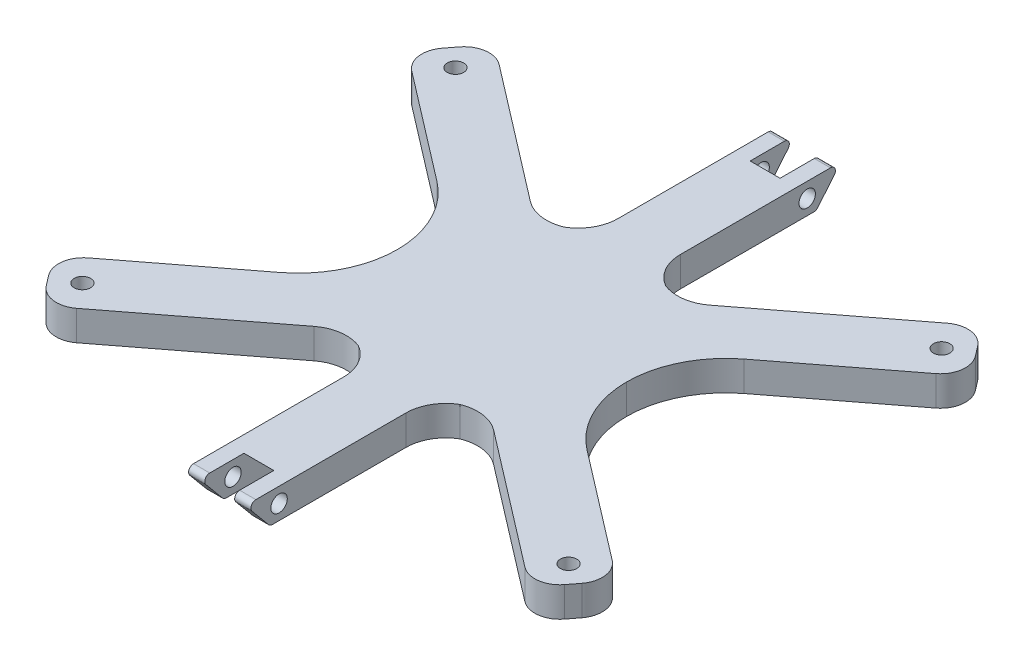
SolidWorks part; units mm, degrees
ref_plane "Front Plane" through (0, 0, 0) normal (0, 0, 1) x (1, 0, 0)
ref_plane "Top Plane" through (0, 0, 0) normal (0, 1, 0) x (1, 0, 0)
ref_plane "Right Plane" through (0, 0, 0) normal (1, 0, 0) x (0, 0, -1)
sketch "Sketch1" plane through (0, 0, 0) normal (0, 1, 0) x (1, 0, 0)
  circle A0 centre (0, 0) radius 23
  dimension "D1" = 46
extrude "Boss-Extrude1" add sketch "Sketch1" along normal mid plane 6
sketch "Sketch2" plane through (0, 0, 0) normal (0, 1, 0) x (1, 0, 0)
  line L0 (-21.3653, 8.5162) -> (-56.5628, 35.5242)
  line L1 (0.2695, -0.2068) -> (-63.7589, 48.924) construction
  line L2 (-48.9532, 45.4411) -> (-13.7557, 18.4331)
  line L3 (0, 37.6664) -> (0, -25.0328) construction
  line L4 (-48.9532, 45.4411) -> (-56.5628, 35.5242)
  circle A0 centre (0, 0) radius 23 construction
  arc A1 (-13.7557, 18.4331) -> (-21.3653, 8.5162) centre (0, 0) ccw
  point P9 (-52.758, 40.4826)
  dimension "D1" = 66.5
  dimension "D2" = 52.5
  dimension "D3" = 12.5
extrude "Boss-Extrude2" add sketch "Sketch2" along normal up to surface and the other way up to surface up to face at (0, 3, 23) other way up to face at (0, -3, 23)
mirror "Mirror1" about plane through (0, 0, 0) normal (1, 0, 0) of "Boss-Extrude2"
mirror "Mirror2" about plane through (0, 0, 0) normal (0, 0, 1) of "Mirror1", "Boss-Extrude2"
sketch "Sketch4" plane through (0, 3, 0) normal (0, 1, 0) x (1, 0, 0)
  line L0 (0, 65.599) -> (0, -44.8835) construction
  line L2 (-6.25, 59.8) -> (6.25, 59.8)
  line L4 (-6.25, 59.8) -> (-6.25, 22.1345)
  line L5 (6.25, 59.8) -> (6.25, 22.1345)
  arc A2 (13.7557, 18.4331) -> (-13.7557, 18.4331) centre (0, 0) ccw construction
  arc A3 (6.25, 22.1345) -> (-6.25, 22.1345) centre (0, 0) ccw
  point P8 (0, 59.8)
  dimension "D1" = 12.5
  dimension "D2" = 59.8
extrude "Boss-Extrude4" add sketch "Sketch4" against normal up to surface (6 mm away) up to face at (0, -3, 0)
mirror "Mirror6" about plane through (0, 0, 0) normal (0, 0, 1) of "Boss-Extrude4"
fillet "Fillet4" radius 8 8 edges at (-13.7557, 0, 18.4331) (-6.25, 0, 22.1345) (6.25, 0, 22.1345) (13.7557, 0, 18.4331) (13.7557, 0, -18.4331) (6.25, 0, -22.1345) (-6.25, 0, -22.1345) (-13.7557, 0, -18.4331)
fillet "Fillet5" radius 20 4 edges at (-21.3653, 0, 8.5162) (-21.3653, 0, -8.5162) (21.3653, 0, 8.5162) (21.3653, 0, -8.5162)
sketch "Sketch3" plane through (0, 3, 0) normal (0, 1, 0) x (1, 0, 0)
  circle A0 centre (-48.7912, 37.4388) radius 1.65
  dimension "D1" = 3.3
  dimension "D2" = 61.5
extrude "Cut-Extrude1" cut sketch "Sketch3" against normal through all
mirror "Mirror3" about plane through (0, 0, 0) normal (1, 0, 0) of "Cut-Extrude1"
mirror "Mirror4" about plane through (0, 0, 0) normal (0, 0, 1) of "Mirror3", "Cut-Extrude1"
sketch "Sketch13" plane through (-6.25, 0, 0) normal (-1, 0, 0) x (0, 0, 1)
  line L0 (-59.8, -3) -> (-59.8, 3) construction
  circle A0 centre (-53, 0) radius 1.65
  point P6 (-59.8, 0)
  dimension "D2" = 3.3
  dimension "D1" = 53
extrude "Cut-Extrude9" cut sketch "Sketch13" against normal blind 14
sketch "Sketch12" plane through (-6.25, 0, 0) normal (-1, 0, 0) x (0, 0, 1)
  line L0 (-59.8, 3) -> (-54.8, -3)
  line L2 (-54.8, -3) -> (-59.8, -3)
  line L3 (-59.8, -3) -> (-59.8, 3)
  line L4 (-27.5307, -3) -> (-59.8, -3) construction
  dimension "D1" = 5
extrude "Cut-Extrude8" cut sketch "Sketch12" against normal up to surface (12.5 mm away) up to face at (6.25, 0, -54.65)
sketch "Sketch14" plane through (0, 3, 0) normal (0, 1, 0) x (1, 0, 0)
  line L0 (-3, 59.8) -> (3, 59.8)
  line L1 (6.25, 59.8) -> (-6.25, 59.8) construction
  line L2 (3, 59.8) -> (3, 50.8)
  line L3 (3, 50.8) -> (-3, 50.8)
  line L4 (-3, 50.8) -> (-3, 59.8)
  point P4 (0, 50.8)
  dimension "D1" = 9
  dimension "D2" = 6
extrude "Cut-Extrude10" cut sketch "Sketch14" against normal blind 14
sketch "Sketch15" plane through (-3, 0, 0) normal (1, 0, 0) x (0, 0, -1)
  line L0 (50.8, 3) -> (40.4826, -3)
  line L1 (45.4411, -3) -> (35.5242, -3) construction
  line L2 (40.4826, -3) -> (50.8, -3)
  line L3 (50.8, -3) -> (50.8, 3)
extrude "Cut-Extrude11" cut sketch "Sketch15" along normal up to surface (6 mm away) up to face at (3, 0, -54.05)
mirror "Mirror8" about plane through (0, 0, 0) normal (0, 0, 1) of "Cut-Extrude11", "Cut-Extrude8", "Cut-Extrude9", "Cut-Extrude10"
fillet "Fillet3" radius 5 8 edges at (48.9532, 0, 45.4411) (56.5628, 0, 35.5242) (56.5628, 0, -35.5242) (48.9532, 0, -45.4411) (-48.9532, 0, -45.4411) (-56.5628, 0, -35.5242) (-56.5628, 0, 35.5242) (-48.9532, 0, 45.4411)
fillet "Fillet7" radius 1 8 edges at (4.625, -3, 54.8) (-4.625, -3, 54.8) (4.625, 3, 59.8) (-4.625, 3, 59.8) (-4.625, -3, -54.8) (4.625, -3, -54.8) (4.625, 3, -59.8) (-4.625, 3, -59.8)
